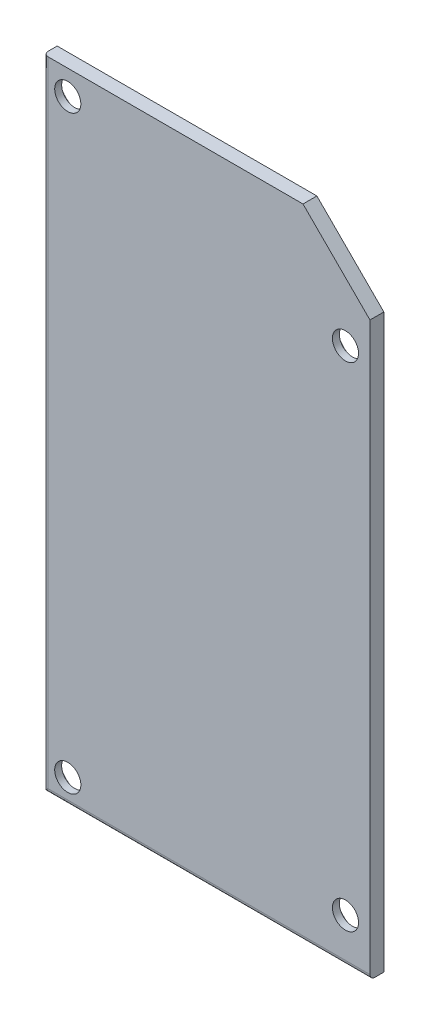
SolidWorks part; units mm, degrees
ref_plane "Front Plane" through (0, 0, 0) normal (0, 0, 1) x (1, 0, 0)
ref_plane "Top Plane" through (0, 0, 0) normal (0, 1, 0) x (1, 0, 0)
ref_plane "Right Plane" through (0, 0, 0) normal (1, 0, 0) x (0, 0, -1)
sketch "Sketch1" plane through (0, 0, 0) normal (0, 0, 1) x (1, 0, 0)
  line L0 (31.8, 78.2) -> (40, 70)
  line L1 (0, 0) -> (40, 0)
  line L3 (0, 78.2) -> (31.8, 78.2)
  line L4 (40, 0) -> (40, 70)
  line L5 (0, 0) -> (0, 3)
  line L6 (6, 75.2) -> (30.5574, 75.2)
  line L7 (35.2, 3) -> (6, 3)
  line L8 (37, 8.4) -> (37, 62.7574)
  line L10 (-74.4457, 75.2) -> (30.5574, 75.2) construction
  line L11 (1.2019, 3) -> (-74.4457, 75.2) construction
  line L12 (30.5574, 75.2) -> (37, 68.7574)
  line L13 (30.5574, 75.2) -> (37, 68.7574) construction
  line L14 (1.2019, 3) -> (37, 3) construction
  line L15 (37, 3) -> (37, 68.7574) construction
  line L16 (0, 78.2) -> (0, 75.2)
  line L17 (-81.934, 78.2) -> (31.8, 78.2) construction
  line L18 (40, 0) -> (40, 70) construction
  line L19 (0, 0) -> (-81.934, 78.2) construction
  arc A0 (37, 68.7574) -> (37, 62.7574) centre (37, 65.7574) ccw
  circle A1 centre (37, 65.7574) radius 1.025
  arc A2 (37, 8.4) -> (35.2, 3) centre (37, 5.4) ccw
  circle A3 centre (37, 5.4) radius 1.025
  arc A4 (6, 3) -> (0, 3) centre (3, 3) ccw
  circle A5 centre (3, 3) radius 1.025
  arc A6 (0, 75.2) -> (6, 75.2) centre (3, 75.2) ccw
  circle A7 centre (3, 75.2) radius 1.025
  dimension "D6" = 6
  dimension "D7" = 2.05
  dimension "D1" = 40
  dimension "D2" = 135
  dimension "D3" = 3
  dimension "D4" = 70
  dimension "D5" = 3
extrude "Boss-Extrude1" add sketch "Sketch1" along normal blind 28
sketch "Sketch2" plane through (0, 78.2, 0) normal (0, 1, 0) x (1, 0, 0)
  line L0 (31.8, -14) -> (-12.3888, -14) construction
  line L1 (31.8, -28) -> (31.8, 0) construction
  circle A0 centre (16.8, -14) radius 13
  dimension "D1" = 26
  dimension "D2" = 15
extrude "Cut-Extrude1" cut sketch "Sketch2" against normal blind 0.6
sketch "Sketch3" plane through (0, 77.6, 0) normal (0, 1, 0) x (1, 0, 0)
  line L0 (16.8, -14) -> (48.7255, -14) construction
  line L2 (26.8399, -12.9) -> (28.0399, -12.9)
  line L4 (26.8399, -15.1) -> (28.0399, -15.1)
  line L5 (28.0399, -12.9) -> (28.0399, -15.1)
  arc A0 (26.8399, -12.9) -> (26.8399, -15.1) centre (16.8, -14) ccw
  dimension "D1" = 20.2
  dimension "D2" = 1.2
  dimension "D3" = 2.2
extrude "Cut-Extrude2" cut sketch "Sketch3" against normal up to next
fillet "Fillet1" radius 0.4 4 edges at (6.7, 77.6, 14) (27.4399, 77.6, 15.1) (28.0399, 77.6, 14) (27.4399, 77.6, 12.9)
sketch "Sketch14" plane through (40, 0, 0) normal (1, 0, 0) x (0, 0, -1)
  line L0 (-14, 70) -> (-14, 0) construction
  line L1 (-28, 70) -> (0, 70) construction
  line L3 (-14, 28) -> (13.9962, 28) construction
  line L4 (-19.9, 47.7) -> (-5.1, 47.7) construction
  line L5 (-15.9, 52.4) -> (-8.1, 52.4)
  line L6 (-19.9, 48.4) -> (-19.9, 47)
  line L7 (-15.9, 43) -> (-8.1, 43)
  line L8 (-8.1, 52.4) -> (-8.1, 43)
  line L9 (-19.2, 57.65) -> (4.7334, 57.65) construction
  line L10 (-19.2, 60.4) -> (-8.8, 60.4)
  line L11 (-19.2, 60.4) -> (-19.2, 54.9)
  line L12 (-19.2, 54.9) -> (-8.8, 54.9)
  line L13 (-8.8, 60.4) -> (-8.8, 54.9)
  line L14 (-7.75, 47.7) -> (3.1305, 47.7) construction
  line L15 (-28, 0) -> (0, 0) construction
  line L17 (-23, 12) -> (-5, 12)
  line L18 (-23, 12) -> (-23, 3)
  line L19 (-23, 3) -> (-5, 3)
  line L20 (-5, 12) -> (-5, 3)
  circle A0 centre (-14, 28) radius 8
  circle A1 centre (-14, 16.9) radius 1.6
  circle A2 centre (-14, 39.1) radius 1.6
  circle A3 centre (-6.3, 47.7) radius 1.45
  circle A4 centre (-21.7, 47.7) radius 1.45
  arc A5 (-15.9, 52.4) -> (-19.9, 48.4) centre (-15.9, 48.4) ccw
  arc A6 (-19.9, 47) -> (-15.9, 43) centre (-15.9, 47) ccw
  circle A7 centre (-22.5, 57.65) radius 1.45
  circle A8 centre (-5.5, 57.65) radius 1.45
  point P27 (-19.9, 52.4)
  point P40 (-19.9, 43)
  dimension "D1" = 16
  dimension "D2" = 3.2
  dimension "D7" = 2.9
  dimension "D9" = 4
  dimension "D13" = 2.9
  dimension "D3" = 22.2
  dimension "D4" = 28
  dimension "D5" = 9.4
  dimension "D6" = 11.8
  dimension "D8" = 15.4
  dimension "D10" = 15
  dimension "D11" = 10.4
  dimension "D12" = 5.5
  dimension "D14" = 17
  dimension "D15" = 2.5
  dimension "D16" = 18
  dimension "D17" = 3
  dimension "D18" = 9
extrude "Cut-Extrude9" cut sketch "Sketch14" against normal through all
fillet "Fillet2" radius 5 8 edges at (35.2, 3, 25.5) (35.2, 3, 2.5) (37, 68.7574, 14) (6, 3, 2.5) (6, 3, 25.5) (37, 8.4, 25.5) (37, 8.4, 2.5) (6, 75.2, 14)
ref_plane "Plane1" through (0, 0, 14) normal (0, 0, 1) x (1, 0, 0)
sketch "Sketch16" plane through (0, 0, 14) normal (0, 0, 1) x (1, 0, 0)
  line L0 (1.975, 3) -> (4.025, 3)
  arc A0 (1.975, 3) -> (4.025, 3) centre (3, 3) ccw
  circle A1 centre (3, 3) radius 1.025 construction
extrude "Boss-Extrude2" add sketch "Sketch16" along normal mid plane 18
sketch "Sketch17" plane through (0, 3, 0) normal (0, 1, 0) x (1, 0, 0)
  line L0 (-22, -14) -> (22, -14) construction
  line L2 (10, -15.7) -> (10, -12.3) construction
  line L3 (4, -15.7) -> (4, -12.3)
  line L4 (16, -15.7) -> (16, -12.3)
  line L5 (-1.8935, -14) -> (39.7453, -14) construction
  arc A1 (4, -15.7) -> (16, -15.7) centre (10, -15.7) ccw
  arc A2 (16, -12.3) -> (4, -12.3) centre (10, -12.3) ccw
  point P8 (10, -14)
  dimension "D3" = 6
  dimension "D4" = 3.4
extrude "Boss-Extrude3" add sketch "Sketch17" along normal blind 1.76
sketch "Sketch18" plane through (0, 4.76, 0) normal (0, 1, 0) x (1, 0, 0)
  line L0 (-1.8826, -14) -> (40.0349, -14) construction
  line L1 (-22, -14) -> (22, -14) construction
  line L2 (10, -15.7) -> (10, -12.3) construction
  line L3 (6.43, -15.7) -> (6.43, -12.3)
  line L4 (13.57, -15.7) -> (13.57, -12.3)
  arc A1 (6.43, -15.7) -> (13.57, -15.7) centre (10, -15.7) ccw
  arc A2 (13.57, -12.3) -> (6.43, -12.3) centre (10, -12.3) ccw
  point P9 (10, -14)
  dimension "D2" = 3.57
  dimension "D3" = 3.4
extrude "Cut-Extrude10" cut sketch "Sketch18" against normal up to next
fillet "Fillet3" radius 5 4 edges at (4, 3, 14) (10, 3, 6.3) (16, 3, 14) (10, 3, 21.7)
sketch "Sketch19" plane through (0, 3, 0) normal (0, 1, 0) x (1, 0, 0)
  line L0 (-1.4647, -14) -> (47.0035, -14) construction
  line L1 (-22, -14) -> (22, -14) construction
  line L2 (29.4343, 0) -> (9.245, 0) construction
  line L3 (40, -22) -> (40, -6) construction
  line L4 (29.4343, -5) -> (29.4343, 0) construction
  circle A0 centre (24, -3.25) radius 1.025
  circle A1 centre (24, -24.75) radius 1.025
  dimension "D1" = 2.05
  dimension "D3" = 3.25
  dimension "D4" = 16
  dimension "D5" = 5.4343
  dimension "D2" = 21.5
extrude "Cut-Extrude11" cut sketch "Sketch19" against normal up to next
fillet "Fillet4" radius 0.6 5 edges at (37, 12, 14) (40, 7.5, 5) (40, 3, 14) (40, 7.5, 23) (40, 12, 14)
sketch "Sketch20" plane through (0, 0, 0) normal (-1, 0, 0) x (0, 0, 1)
  line L0 (14, 87.38) -> (14, -6.6146) construction
  line L1 (14, -22) -> (14, 22) construction
  line L2 (5, 3) -> (5, 109.2462) construction
  line L3 (23, 3) -> (23, 109.2462) construction
  line L4 (28, 75.2) -> (0, 75.2) construction
  line L5 (23, 75.2) -> (5, 75.2)
  line L6 (23, 75.2) -> (23, 72.2)
  line L7 (23, 72.2) -> (5, 72.2)
  line L8 (5, 75.2) -> (5, 72.2)
  line L9 (0, 72.2) -> (28, 72.2) construction
extrude "Cut-Extrude12" cut sketch "Sketch20" against normal up to next
sketch "Sketch21" plane through (0, 0, 14) normal (0, 0, 1) x (1, 0, 0)
  line L0 (1.975, 75.2) -> (4.025, 75.2)
  arc A0 (4.025, 75.2) -> (1.975, 75.2) centre (3, 75.2) ccw
extrude "Boss-Extrude4" add sketch "Sketch21" along normal mid plane 18
fillet "Fillet5" radius 2.5 1 edges at (37, 62.7574, 14)
sketch "Sketch22" plane through (0, 0, 28) normal (0, 0, 1) x (1, 0, 0)
  line L0 (0, 78.2) -> (31.8, 78.2)
  line L1 (31.8, 78.2) -> (40, 70)
  line L2 (40, 70) -> (40, 0)
  line L3 (40, 0) -> (0, 0)
  line L4 (0, 0) -> (0, 78.2)
  line L5 (1.975, 75.2) -> (4.025, 75.2) construction
  circle A0 centre (3, 75.2) radius 1.6
  circle A1 centre (37, 65.7574) radius 1.6
  circle A2 centre (37, 5.4) radius 1.6
  circle A3 centre (3, 3) radius 1.6
  dimension "D1" = 3.2
extrude "Boss-Extrude5" add sketch "Sketch22" along normal blind 1.7
sketch "Sketch23" plane through (0, 0, 28) normal (0, 0, -1) x (-1, 0, 0)
  line L1 (-46.1974, 80.9815) -> (11.5404, 80.9815)
  line L2 (-46.1974, 80.9815) -> (-46.1974, -7.2626)
  line L3 (-46.1974, -7.2626) -> (11.5404, -7.2626)
  line L4 (11.5404, 80.9815) -> (11.5404, -7.2626)
extrude "Cut-Extrude13" cut sketch "Sketch23" along normal through all
sketch "Sketch24" plane through (0, 0, 28) normal (0, 0, 1) x (1, 0, 0)
  circle A0 centre (3, 75.2) radius 2.75
  circle A1 centre (37, 65.7574) radius 2.75
  circle A2 centre (3, 3) radius 2.75
  circle A3 centre (37, 5.4) radius 2.75
  dimension "D1" = 5.5
extrude "Cut-Extrude14" cut sketch "Sketch24" along normal blind 0.85
fillet "Fillet7" radius 0.6 2 edges at (20, 0, 29.7) (0, 39.1, 29.7)
